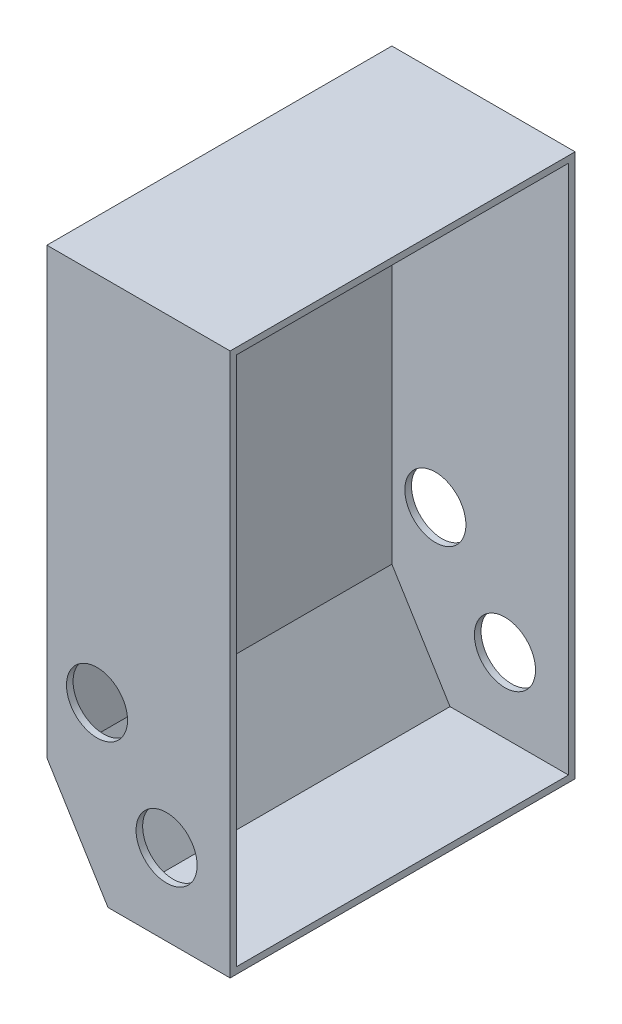
SolidWorks part; units mm, degrees
ref_plane "Front Plane" through (0, 0, 0) normal (1, 0, 0) x (0, 1, 0)
ref_plane "Top Plane" through (0, 0, 0) normal (0, 0, 1) x (0, 1, 0)
ref_plane "Right Plane" through (0, 0, 0) normal (0, 1, 0) x (-1, 0, 0)
sketch "Sketch1" plane through (0, 0, 0) normal (1, 0, 0) x (0, 1, 0)
  line L0 (129, 106) -> (129, 103)
  line L1 (0, 0) -> (329, 0)
  line L2 (0, 0) -> (0, 209)
  line L4 (329, 0) -> (329, 209)
  line L5 (0, 106) -> (329, 106)
  line L6 (0, 106) -> (0, 103)
  line L7 (0, 103) -> (329, 103)
  line L8 (329, 106) -> (329, 103)
  line L9 (63, 209) -> (66, 209)
  line L10 (0, 209) -> (63, 209)
  line L11 (63, 209) -> (126, 209)
  line L12 (126, 209) -> (329, 209)
  line L13 (126, 209) -> (129, 209)
  line L14 (63, 209) -> (63, 106)
  line L15 (63, 106) -> (66, 106)
  line L16 (66, 209) -> (66, 106)
  line L17 (63, 103) -> (66, 103)
  line L18 (63, 103) -> (63, 0)
  line L19 (63, 0) -> (66, 0)
  line L20 (66, 103) -> (66, 0)
  line L21 (126, 209) -> (126, 106)
  line L22 (126, 106) -> (129, 106)
  line L23 (129, 209) -> (129, 106)
  line L24 (126, 103) -> (129, 103)
  line L25 (126, 103) -> (126, 0)
  line L26 (126, 0) -> (129, 0)
  line L27 (129, 103) -> (129, 0)
  line L28 (126, 106) -> (126, 103)
  line L29 (66, 106) -> (66, 103)
  line L30 (63, 106) -> (63, 103)
  dimension "D1" = 3
  dimension "D2" = 3
  dimension "D3" = 63
  dimension "D4" = 103
  dimension "D5" = 203
  dimension "D6" = 3
extrude "Boss-Extrude1" add sketch "Sketch1" along normal blind 111 contours L14 L10 L2 L5 | L18 L7 L2 L1 | L25 L7 L20 L1 | L21 L11 L16 L5 | L12 L23 L5 L4 | L7 L27 L1 L4 | L27 L7 L25 L1 | L0 L7 L4 L5 | L5 L29 L7 L28 | L23 L12 L21 L5 | L16 L9 L14 L5 | L20 L7 L18 L1 | L5 L28 L7 L0 | L5 L8 L7 L6 region at (0, 229, 104.5) region at (0, 127.5, 104.5) region at (0, 229, 157.5) region at (0, 127.5, 157.5) region at (0, 127.5, 51.5) region at (0, 229, 51.5) region at (0, 96, 104.5) region at (0, 96, 157.5) region at (0, 96, 51.5) region at (0, 64.5, 157.5) region at (0, 64.5, 51.5) region at (0, 31.5, 157.5) region at (0, 31.5, 51.5)
chamfer "Chamfer1" distance 37 distance2 60 1 edges at (0, 0, 104.5) first distance on face at (55.5, 0, 104.5)
shell "Shell1" thickness 4 removed face at (111, 164.5, 104.5)
sketch "Sketch4" plane through (0, 0, 4) normal (0, 0, 1) x (1, 0, 0)
  circle A0 centre (72.5033, 49.0694) radius 18.5
  circle A1 centre (30.3543, 104.1504) radius 18.5
  point P4 (33.2281, 105.5873)
  point P5 (72.5033, 49.0694)
  point P6 (30.3543, 104.1504)
  dimension "D1" = 37
extrude "Cut-Extrude1" cut sketch "Sketch4" against normal up to next and the other way through all
equation "\"MotorDriverLength\"= 60mm"
equation "\"MotorLength\"= 60"
equation "\"MotorDriverWidth\"= 40"
equation "\"MotorWidth\"= 37"
equation "\"InnerWallThickness\"=3"
equation "\"D1@Sketch1\"=\"InnerWallThickness\""
equation "\"D2@Sketch1\"=\"InnerWallThickness\""
equation "\"D3@Sketch1\"=\"MotorDriverLength\"+\"InnerWallThickness\""
equation "\"D4@Sketch1\"=\"MotorLength\"+\"MotorDriverWidth\"+\"InnerWallThickness\""
equation "\"D6@Sketch1\"=\"InnerWallThickness\""
equation "\"BatteryWidth\"=200"
equation "\"D5@Sketch1\"=\"BatteryWidth\"+\"InnerWallThickness\""
equation "\"ChassisHeight\"=140000"
equation "\"D1@Boss-Extrude1\"=\"CompartmentHeight\"*3"
equation "\"OutterWallThickness\"=4"
equation "\"D1@Shell1\"=\"OutterWallThickness\""
equation "\"D1@Chamfer1\"=\"CompartmentHeight\""
equation "\"CompartmentHeight\"=37"
equation "\"CompartmentWidth\" = \"MotorDriverLength\""
equation "\"D3@Chamfer1\"=\"CompartmentWidth\""
equation "\"MotorDiameter\"=37"
equation "\"D1@Sketch4\"=\"MotorDiameter\""
